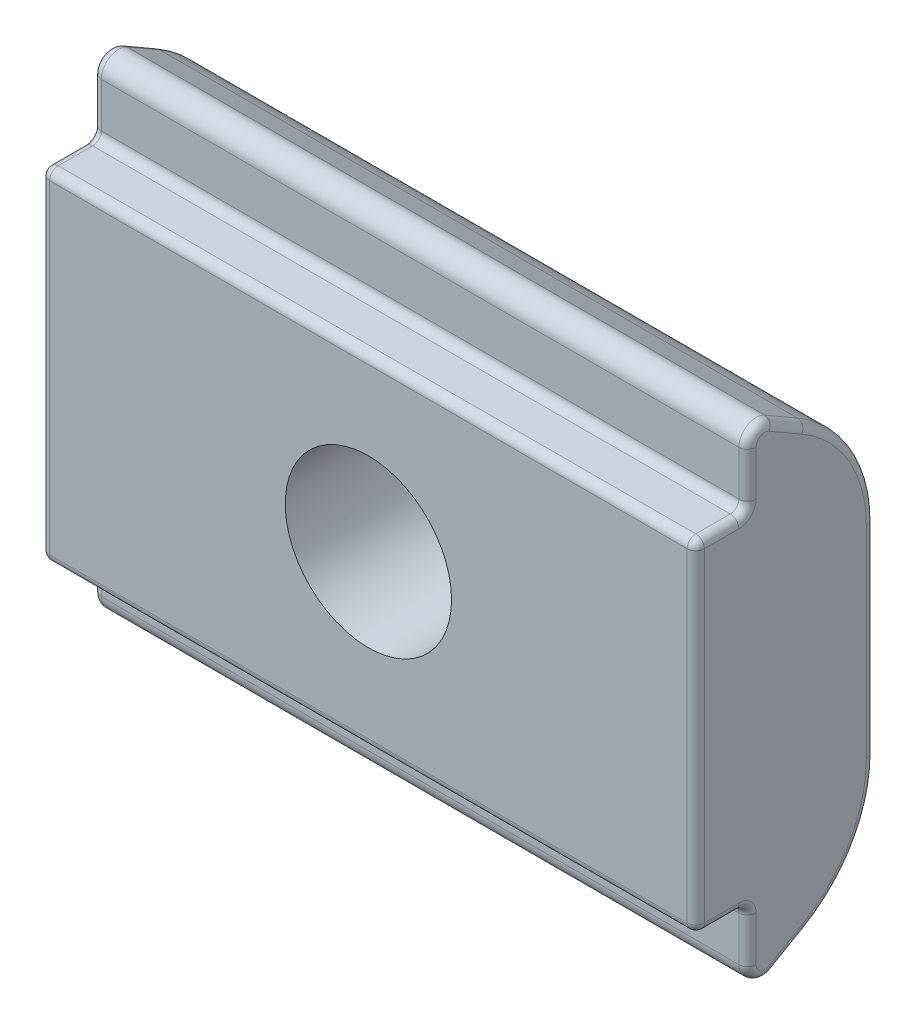
SolidWorks part; units mm, degrees
ref_plane "Front Plane" through (0, 0, 0) normal (0, 0, 1) x (1, 0, 0)
ref_plane "Top Plane" through (0, 0, 0) normal (0, 1, 0) x (1, 0, 0)
ref_plane "Right Plane" through (0, 0, 0) normal (1, 0, 0) x (0, 0, -1)
sketch "Sketch1" plane through (0, 0, 0) normal (0, 0, 1) x (1, 0, 0)
  line L1 (-9.5, 7) -> (9.5, 7)
  line L2 (-9.5, 7) -> (-9.5, -7)
  line L3 (-9.5, -7) -> (9.5, -7)
  line L4 (9.5, 7) -> (9.5, -7)
  circle A0 centre (0, 0) radius 2.413
  point P4 (0, 7)
  point P5 (0, 0)
  point P6 (-9.5, 0)
  point P11 (0, 2.413)
  dimension "Thread Diameter" = 4.826
  dimension "Length" = 19
  dimension "Width" = 14
sketch "Sketch2" plane through (0, 0, 0) normal (1, 0, 0) x (0, 0, -1)
  line L0 (-2.6, -4.95) -> (-2.6, 4.95)
  line L1 (-2.6, 4.95) -> (-1.1, 4.95)
  line L4 (-2.6, -4.95) -> (-1.1, -4.95)
  line L8 (-2.6, 0) -> (2.6, 0)
  line L13 (-3.3441, 2.4989) -> (-2.9473, 1.8115)
  line L14 (-2.9473, 1.8115) -> (-2.5504, 2.4989)
  line L15 (-2.5504, 2.4989) -> (-3.3441, 2.4989)
  line L16 (-2.9473, 2.4989) -> (-2.9473, 2.413)
  line L17 (-2.9473, 1.8115) -> (-2.9473, 1.8974)
  line L18 (-3.2945, 2.413) -> (-2.6, 2.413)
  line L19 (-3.3193, 2.456) -> (-2.5752, 2.456)
  line L20 (-2.9969, 1.8974) -> (-2.8977, 1.8974)
  point P12 (0, 0)
  point P39 (-2.9473, 2.413)
  point P42 (-2.9473, 2.456)
  point P45 (-2.9473, 1.8974)
  dimension "Thickness" = 5.2
  dimension "Step Width" = 9.9
  dimension "Step Thickness" = 1.5
  dimension "Thread Pitch" = 0.7937
  dimension "D12" = 0.0992
sketch "Sketch4" plane through (0, 0, 0) normal (1, 0, 0) x (0, 0, -1)
  line L0 (-0.35, 6.933) -> (0.6, 6.3845)
  line L1 (-0.35, -6.933) -> (0.6, -6.3845)
  line L3 (-2.6, -4.95) -> (-1.1, -4.95) construction
  line L4 (-2.6, -4.95) -> (-2.6, 4.95) construction
  line L5 (-2.6, 4.95) -> (-1.1, 4.95) construction
  line L11 (-2.6, -4.95) -> (-1.1, -4.95)
  line L12 (-2.6, -4.95) -> (-2.6, 4.95)
  line L13 (-2.6, 4.95) -> (-1.1, 4.95)
  line L16 (-1.1, 4.95) -> (-1.1, 6.5)
  line L17 (-1.1, -4.95) -> (-1.1, -6.5)
  line L18 (2.6, 2.9204) -> (2.6, -2.9204)
  arc A0 (0.6, -6.3845) -> (2.6, -2.9204) centre (-1.4, -2.9204) ccw
  arc A1 (2.6, 2.9204) -> (0.6, 6.3845) centre (-1.4, 2.9204) ccw
  arc A10 (-0.35, -6.933) -> (-1.1, -6.5) centre (-0.6, -6.5) cw
  arc A11 (-0.35, 6.933) -> (-1.1, 6.5) centre (-0.6, 6.5) ccw
  point P14 (-0.6, 7)
  dimension "D1" = 0.5
  dimension "D2" = 4
  dimension "D3" = 60
extrude "Boss-Extrude1" add sketch "Sketch4" against normal up to vertex (9.5 mm away) and the other way up to vertex (9.5 mm away) up to point (-9.5, 7, 0) other way up to point (9.5, 7, 0)
sketch "Sketch6" plane through (0, 0, 2.6) normal (0, 0, 1) x (1, 0, 0)
  circle A0 centre (0, 0) radius 2.413 construction
  circle A1 centre (0, 0) radius 2.413
extrude "Cut-Extrude2" cut sketch "Sketch6" against normal through all
fillet "Fillet5" radius 0.25 28 edges at (-9.5, 4.95, 1.85) (9.5, 4.95, 1.85) (-9.5, -4.95, 1.85) (9.5, -4.95, 1.85) (-9.5, 5.725, 1.1) (-9.5, 6.933, 0.85) (9.5, 5.725, 1.1) (9.5, 6.933, 0.85) (-9.5, -6.6588, -0.125) (-9.5, -6.933, 0.85) (9.5, -6.6588, -0.125) (9.5, -6.933, 0.85) (-9.5, 0, -2.6) (-9.5, 6.6588, -0.125) (9.5, 0, -2.6) (9.5, 6.6588, -0.125) (9.5, 0, 2.6) (-9.5, 0, 2.6) (-9.5, -5.725, 1.1) (9.5, -5.725, 1.1) (0, -4.95, 1.1) (0, -4.95, 2.6) (0, 4.95, 2.6) (0, 4.95, 1.1) (-9.5, 4.9204, -2.0641) (-9.5, -4.9204, -2.0641) (9.5, 4.9204, -2.0641) (9.5, -4.9204, -2.0641)
sketch "Sketch9" plane through (0, 0, 0) normal (0, 0, 1) x (1, 0, 0)
  line L0 (0, 0) -> (1.7062, -1.7062)
  line L2 (-9.5, 7) -> (9.5, 7) construction
  circle A0 centre (0, 0) radius 2.413 construction
  circle A1 centre (0, 0) radius 2.413
  point P0 (-9.5, 7)
  point P1 (9.5, 7)
  point P3 (-9.5, -7)
  point P13 (1.7062, -1.7062)
  dimension "D1" = 45
sketch "Sketch10" plane through (0, 0, 0) normal (1, 0, 0) x (0, 0, -1)
  line L0 (-2.6, -4.95) -> (-1.1, -4.95) construction
  point P0 (-2.6, 4.95)
  point P1 (2.6, 4.95)
  point P3 (2.6, -4.95)
  point P5 (-2.6, -4.95)
sketch "Sketch11" [suppressed] plane through (0, 0, 2.6) normal (0, 0, 1) x (1, 0, 0)
  circle A0 centre (0, 0) radius 2.413
curve "Helix/Spiral1" [suppressed] pitch 0.7937 height 5.9938 turns 7.5512
sketch "Sketch12" [suppressed] plane through (0, 0, 0) normal (1, 0, 0) x (0, 0, -1)
  line L0 (-2.9969, 1.8974) -> (-2.8977, 1.8974) construction
  line L1 (-3.3441, 2.4989) -> (-2.9473, 1.8115) construction
  line L2 (-2.9473, 1.8115) -> (-2.5504, 2.4989) construction
  line L3 (-3.3193, 2.456) -> (-2.5752, 2.456) construction
  line L4 (-2.9969, 1.8974) -> (-2.8977, 1.8974)
  line L5 (-3.3193, 2.456) -> (-2.9969, 1.8974)
  line L6 (-2.8977, 1.8974) -> (-2.5752, 2.456)
  line L7 (-3.3193, 2.456) -> (-2.5752, 2.456)
sweep "Sweep1" [suppressed] add profiles "Sketch12" path "Helix/Spiral1"
sketch "Sketch13" [suppressed] plane through (0, 0, 2.6) normal (0, 0, 1) x (1, 0, 0)
  circle A0 centre (0, 0) radius 2.4989
extrude "Cut-Extrude4" [suppressed] cut sketch "Sketch13" against normal through all draft 45 and the other way through all
sketch "Sketch15" [suppressed] plane through (9.5, 0, 0) normal (1, 0, 0) x (0, 0, -1)
  line L1 (2.6, 2.9204) -> (2.6, -2.9204) construction
  line L3 (2.6, 2.9204) -> (2.6, -2.9204)
  line L4 (0.6, 6.3845) -> (13.3691, 6.3845)
  line L5 (13.3691, 6.3845) -> (13.3691, -6.3845)
  line L6 (13.3691, -6.3845) -> (0.6, -6.3845)
  arc A0 (0.6, -6.3845) -> (2.6, -2.9204) centre (-1.4, -2.9204) ccw construction
  arc A1 (2.6, 2.9204) -> (0.6, 6.3845) centre (-1.4, 2.9204) ccw construction
  arc A2 (0.6, -6.3845) -> (2.6, -2.9204) centre (-1.4, -2.9204) ccw
  arc A3 (2.6, 2.9204) -> (0.6, 6.3845) centre (-1.4, 2.9204) ccw
extrude "Cut-Extrude6" [suppressed] cut sketch "Sketch15" against normal through all
sketch "Sketch14" [suppressed] plane through (0, 0, -2.6) normal (0, 0, -1) x (-1, 0, 0)
  circle A1 centre (0, 0) radius 2.4989
  circle A2 centre (0, 0) radius 2.4989
  dimension "D1" = 0
extrude "Cut-Extrude5" [suppressed] cut sketch "Sketch14" along normal through all and the other way blind 10 draft 45
equation "\"D12@Sketch2\"=\"Thread Pitch@Sketch2\"/8"
equation "\"D3@Helix/Spiral1\"=\"Thickness@Sketch2\"+\"Thread Pitch@Sketch2\""
equation "\"D4@Helix/Spiral1\"=\"Thread Pitch@Sketch2\""
